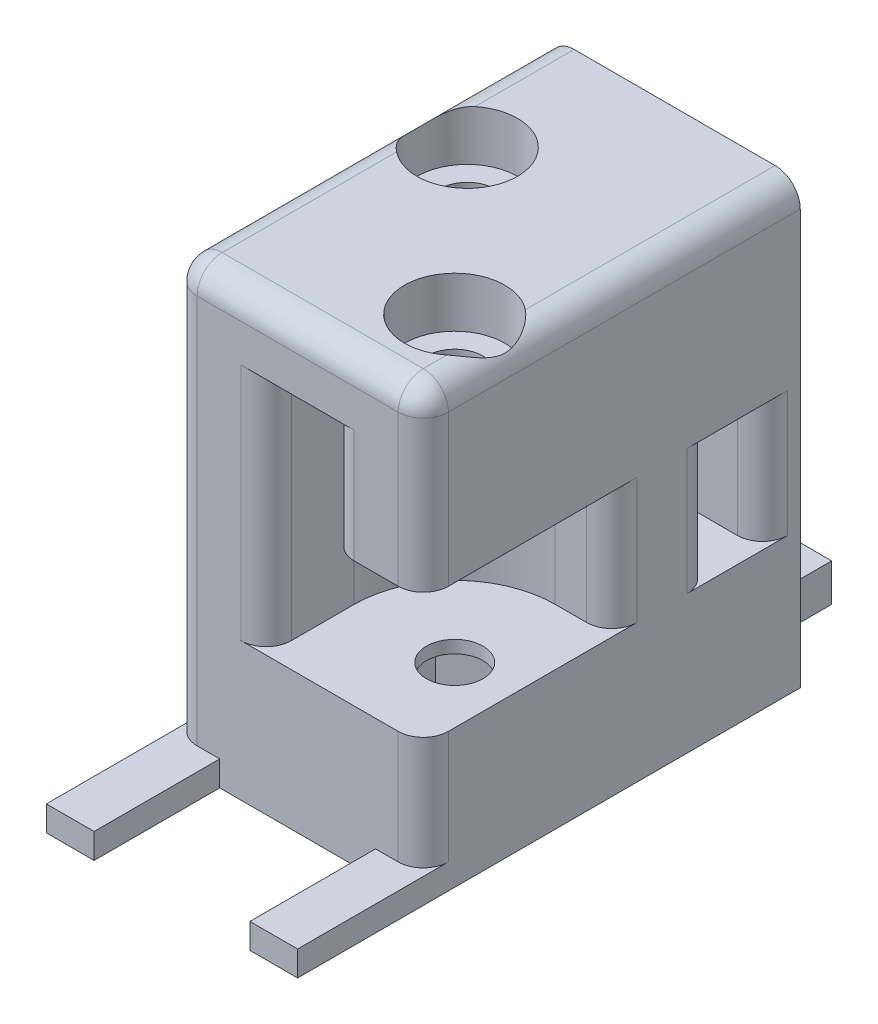
SolidWorks part; units mm, degrees
material "ABS"
ref_plane "Front Plane" through (0, 0, 0) normal (0, 0, 1) x (1, 0, 0)
ref_plane "Top Plane" through (0, 0, 0) normal (0, 1, 0) x (1, 0, 0)
ref_plane "Right Plane" through (0, 0, 0) normal (1, 0, 0) x (0, 0, -1)
sketch "Sketch2" plane through (0, 0, 0) normal (0, 1, 0) x (1, 0, 0)
  line L1 (-10, -15) -> (10, -15)
  line L2 (-10, -15) -> (-10, 15)
  line L3 (-10, 15) -> (10, 15)
  line L4 (10, -15) -> (10, 15)
  line L5 (-10, -15) -> (10, 15) construction
  line L6 (-10, 15) -> (10, -15) construction
  point P0 (0, 0)
  dimension "D1" = 20
  dimension "D2" = 30
extrude "Boss-Extrude1" add sketch "Sketch2" along normal blind 30
sketch "Sketch3" plane through (0, 30, 0) normal (0, 1, 0) x (1, 0, 0)
  line L0 (0, -15) -> (0, 15) construction
  line L1 (-10, -15) -> (10, -15) construction
  line L2 (10, 15) -> (-10, 15) construction
  line L3 (5.5, -1) -> (10, -1)
  line L4 (10, -15) -> (10, 15) construction
  line L6 (-5.5, 11) -> (-10, 11)
  line L7 (-10, 15) -> (-10, -15) construction
  line L8 (-10, 11) -> (-10, -1.3619)
  line L9 (-1.5, -8) -> (-1.5, -1.7446)
  line L10 (1.5, 4) -> (1.5, -2.2554)
  line L11 (-1.5, -8) -> (-1.5, -15)
  line L12 (1.5, -15) -> (1.5, -13.7446)
  line L13 (10, 11) -> (-5.5, 11)
  line L14 (10, 11) -> (10, 8)
  line L15 (10, 8) -> (0.2446, 8)
  line L17 (10, -15) -> (10, -1)
  line L18 (1.5, -15) -> (10, -15)
  line L19 (-5.5, -3) -> (-10, -3)
  line L20 (-10, -3) -> (-10, -1.3619)
  circle A0 centre (5.5, -8) radius 2.25
  circle A1 centre (-5.5, 4) radius 2.25
  arc A2 (5.5, -1) -> (1.5, -13.7446) centre (5.5, -8) ccw
  arc A3 (-5.5, 11) -> (-10, -1.3619) centre (-5.5, 4) cw
  line M1 (10, -15) -> (10, 15)
  line M3 (-10, 15) -> (-10, -15)
  line M4 (-10, -15) -> (10, -15)
  dimension "D3" = 4.5
  dimension "D4" = 4.5
  dimension "D7" = 7
  dimension "D8" = 7
  dimension "D1" = 5.5
  dimension "D2" = 7
  dimension "D5" = 12
  dimension "D6" = 5.5
  dimension "D9" = 3
extrude "Cut-Extrude2" cut sketch "Sketch3" against normal blind 19 contours L0 A2 L3 A0 M1 | A2 L0 | A3 L0 L6 A1 M3 | L0 A3 | L0 A2 L10 A3 | A2 L0 A3 L9 | L0 A2 L11 M4 | L0 L12 A2 M4 | L0 L15 L13 M1 | L15 L0 L13 A3 | L19 A3 M3 region at (-0.8553, 30, 12.8515) region at (0.6574, 30, 14.0101) region at (-0.6059, 30, 8) region at (0.172, 30, 8) region at (-0.8136, 30, 3.1846) region at (0.8136, 30, 0.8154) region at (-0.8157, 30, 0.9677) region at (0.6059, 30, -4) region at (-8.903, 30, 2.5203) region at (-1.3171, 30, -10.2343) region at (5.0068, 30, -9.5019)
sketch "Sketch5" plane through (0, 30, 0) normal (0, 1, 0) x (1, 0, 0)
  line L1 (10, -15) -> (-10, -15)
  line L2 (10, -15) -> (10, 15)
  line L3 (10, 15) -> (-10, 15)
  line L4 (-10, -15) -> (-10, 15)
  line L5 (10, -15) -> (-10, 15) construction
  line L6 (10, 15) -> (-10, -15) construction
  point P0 (0, 0)
extrude "Boss-Extrude2" add sketch "Sketch5" along normal blind 5
sketch "Sketch6" plane through (0, 30, 0) normal (0, -1, 0) x (1, 0, 0)
  line L3 (-1.5, 15) -> (10, 15) construction
  line L8 (1.5, 2.2554) -> (1.5, 15)
  line L9 (-1.5, 15) -> (10, 15) construction
  line L10 (1.5, 15) -> (10, 15)
  line L11 (10, 15) -> (10, 1)
  line L12 (10, 1) -> (5.5, 1)
  line L13 (5.5, 1) -> (10, 1) construction
  circle A0 centre (5.5, 8) radius 2.2812
  arc A1 (5.5, 1) -> (1.5, 2.2554) centre (5.5, 8) cw
extrude "Boss-Extrude3" add sketch "Sketch6" along normal blind 9
sketch "Sketch7" plane through (0, 11, 0) normal (0, 1, 0) x (1, 0, 0)
  line L0 (0.2446, 8) -> (-10, 8)
  line L1 (-5.5, -3) -> (-10, -3)
  line L2 (-10, 11) -> (-10, -3) construction
  line L3 (-1.5, -15) -> (-1.5, -1.7446) construction
  line L4 (-1.5, -1.7446) -> (-1.5, -8)
  line L5 (1.5, -2.2554) -> (1.5, 4)
  line L6 (1.5, 4) -> (1.5, -2.2554) construction
  line L7 (-10, 8) -> (-10, -3)
  arc A0 (0.2446, 8) -> (1.5, 4) centre (-5.5, 4) cw
  arc A1 (-1.5, -1.7446) -> (-5.5, -3) centre (-5.5, 4) cw
  arc A2 (-5.5, -3) -> (-1.5, -1.7446) centre (-5.5, 4) ccw construction
  arc A3 (1.5, -2.2554) -> (-1.5, -8) centre (5.5, -8) ccw
  circle A4 centre (-5.5, 4) radius 2.25
  arc A5 (-5.5, -3) -> (-1.5, -1.7446) centre (-5.5, 4) ccw construction
extrude "Boss-Extrude4" add sketch "Sketch7" along normal blind 9 contours A3 L0 region at (-4.0921, 11, -2.1111)
sketch "Sketch15" plane through (0, 30, 0) normal (0, -1, 0) x (1, 0, 0)
  line L0 (10, -11) -> (-10, -11) construction
  line L5 (10, -8) -> (10, -11)
  line L6 (10, -11) -> (-5.5, -11)
  line L7 (0.2446, -8) -> (10, -8)
  arc A0 (0.2446, -8) -> (-5.5, -11) centre (-5.5, -4) cw
extrude "Boss-Extrude6" add sketch "Sketch15" along normal blind 9
sketch "Sketch16" [suppressed] plane through (0, 11, 0) normal (0, 1, 0) x (1, 0, 0)
  line L0 (10, -15) -> (10, -1)
  line L1 (10, -1) -> (5.5, -1)
  line L2 (10, -15) -> (1.5, -15)
  line L3 (-1.5, -15) -> (10, -15) construction
  line L4 (1.5, -15) -> (1.5, -2.2554)
  circle A0 centre (5.5, -8) radius 2.25
  arc A1 (5.5, -1) -> (1.5, -2.2554) centre (5.5, -8) ccw construction
  arc A2 (1.5, -2.2554) -> (5.5, -1) centre (5.5, -8) cw
  dimension "D1" = 3
extrude "Boss-Extrude7" [suppressed] add sketch "Sketch16" along normal blind 9
sketch "Sketch17" [suppressed] plane through (0, 30, 0) normal (0, -1, 0) x (1, 0, 0)
  line L0 (0.2446, -8) -> (-10, -8)
  line L1 (-10, -11) -> (-10, 3) construction
  line L2 (-10, -8) -> (-10, 3)
  line L3 (1.5, -4) -> (1.5, 2.2554) construction
  line L4 (1.5, -4) -> (1.5, 2.2554)
  line L5 (-1.5, 8.0934) -> (-1.5, 1.7446)
  line L6 (-1.5, 15) -> (-1.5, 1.7446) construction
  line L7 (-5.5, 3) -> (-10, 3)
  line L8 (-5.5, 3) -> (-10, 3) construction
  circle A0 centre (-5.5, -4) radius 2.25
  arc A1 (-1.5, 1.7446) -> (-5.5, 3) centre (-5.5, -4) ccw
  arc A2 (-1.5, 1.7446) -> (-5.5, 3) centre (-5.5, -4) ccw construction
  arc A3 (0.2446, -8) -> (1.5, -4) centre (-5.5, -4) ccw
  arc A4 (1.5, 2.2554) -> (-1.5, 8) centre (5.5, 8) cw
  arc A5 (-1.5, 1.7446) -> (-5.5, 3) centre (-5.5, -4) ccw construction
extrude "Boss-Extrude8" [suppressed] add sketch "Sketch17" along normal blind 9
sketch "Sketch18" [suppressed] plane through (0, 11, 0) normal (0, 1, 0) x (1, 0, 0)
  line L0 (10, 11) -> (10, 8)
  line L1 (10, 8) -> (0.2446, 8)
  line L2 (10, 11) -> (-10, 11) construction
  line L3 (10, 11) -> (-5.5, 11)
  arc A0 (0.2446, 8) -> (-5.5, 11) centre (-5.5, 4) ccw
extrude "Boss-Extrude9" [suppressed] add sketch "Sketch18" along normal blind 9
sketch "Sketch9" plane through (0, 0, -15) normal (0, 0, -1) x (-1, 0, 0)
  line L0 (-10, 0) -> (10, 0) construction
  line L1 (-5.5, 3) -> (5.5, 3)
  line L2 (-5.5, 3) -> (-5.5, 0)
  line L3 (-5.5, 0) -> (5.5, 0)
  line L4 (5.5, 3) -> (5.5, 0)
  line L5 (-5.5, 3) -> (5.5, 0) construction
  line L6 (-5.5, 0) -> (5.5, 3) construction
  line L9 (-10, 35) -> (-10, 0) construction
  point P0 (0, 1.5)
  dimension "D1" = 3
  dimension "D2" = 11
  dimension "D3" = 4.5
extrude "Boss-Extrude5" add sketch "Sketch9" along normal blind 7
sketch "Sketch10" plane through (0, 3, 0) normal (0, 1, 0) x (1, 0, 0)
  line L0 (-5.5, 15) -> (5.5, 15) construction
  circle A0 centre (0, 18.5) radius 1.75
  dimension "D1" = 3.5
  dimension "D2" = 3.5
extrude "Cut-Extrude4" cut sketch "Sketch10" against normal through all
sketch "Sketch11" plane through (0, 3, 0) normal (0, 1, 0) x (1, 0, 0)
  circle A0 centre (0, 18.5) radius 3
  dimension "D1" = 6
extrude "Cut-Extrude5" cut sketch "Sketch11" against normal blind 1
sketch "Sketch8" plane through (0, 35, 0) normal (0, 1, 0) x (1, 0, 0)
  line L0 (0, -15) -> (0, 15) construction
  line L1 (-10, -15) -> (10, -15) construction
  line L2 (10, 15) -> (-10, 15) construction
  circle A0 centre (5.5, -8) radius 2.25
  circle A1 centre (-5.5, 4) radius 2.25
  dimension "D1" = 4.5
  dimension "D2" = 4.5
  dimension "D3" = 7
  dimension "D4" = 5.5
  dimension "D5" = 5.5
  dimension "D6" = 12
extrude "Cut-Extrude3" cut sketch "Sketch8" against normal through all
hole_wizard "CBORE for M4 Hex Socket Head Cap Screw1" positions "Sketch12" profile "Sketch13" counterbore size "M4" standard "ISO" end condition up to next
sketch "Sketch12" plane through (0, 35, 0) normal (0, 1, 0) x (1, 0, 0)
  point P0 (5.5, -8)
  point P3 (-5.5, 4)
sketch "Sketch13" plane through (5.5, 35, 8) normal (1, 0, 0) x (0, 0, 1)
  line L0 (0, 0) -> (0, 35)
  line L1 (0, 35) -> (2.25, 35)
  line L3 (2.25, 35) -> (2.25, 4)
  line L4 (2.25, 4) -> (4, 4)
  line L5 (4, 4) -> (4, 0)
  line L7 (4, 0) -> (0, 0)
  line L11 (0, -6.35) -> (0, 107.95) construction
  dimension "Thru Hole Dia." = 4.5
  dimension "Thru Hole Depth" = 35
  dimension "C'Bore Dia." = 8
  dimension "C'Bore Depth" = 4
sketch "Sketch14" plane through (0, 0, 0) normal (0, -1, 0) x (1, 0, 0)
  line L1 (5.5, 3.8142) -> (9.125, 5.9071)
  line L2 (9.125, 5.9071) -> (9.125, 10.0929)
  line L3 (9.125, 10.0929) -> (5.5, 12.1858)
  line L4 (5.5, 12.1858) -> (1.875, 10.0929)
  line L5 (1.875, 10.0929) -> (1.875, 5.9071)
  line L6 (1.875, 5.9071) -> (5.5, 3.8142)
  line L7 (-5.5, -8.1858) -> (-1.875, -6.0929)
  line L8 (-1.875, -6.0929) -> (-1.875, -1.9071)
  line L9 (-1.875, -1.9071) -> (-5.5, 0.1858)
  line L10 (-5.5, 0.1858) -> (-9.125, -1.9071)
  line L11 (-9.125, -1.9071) -> (-9.125, -6.0929)
  line L12 (-9.125, -6.0929) -> (-5.5, -8.1858)
  circle A0 centre (5.5, 8) radius 3.625 construction
  circle A1 centre (-5.5, -4) radius 3.625 construction
  dimension "D1" = 7.25
  dimension "D2" = 7.25
extrude "Cut-Extrude6" cut sketch "Sketch14" against normal blind 10
sketch "Sketch19" plane through (0, 0, 15) normal (0, 0, 1) x (1, 0, 0)
  line L1 (-10, 0) -> (-6.2, 0)
  line L2 (-10, 0) -> (-10, 2)
  line L3 (-10, 2) -> (-6.2, 2)
  line L4 (-6.2, 0) -> (-6.2, 2)
  line L5 (10, 0) -> (6.2, 0)
  line L6 (10, 0) -> (10, 2)
  line L7 (10, 2) -> (6.2, 2)
  line L8 (6.2, 0) -> (6.2, 2)
  dimension "D1" = 3.8
  dimension "D2" = 3.8
  dimension "D3" = 2
  dimension "D4" = 2
extrude "Boss-Extrude10" add sketch "Sketch19" along normal blind 10
sketch "Sketch21" [suppressed] plane through (0, 20, 0) normal (0, 1, 0) x (1, 0, 0)
  line L3 (10, 0) -> (5.5, 0)
  line L4 (10, -15) -> (-2.5, -15)
  line L5 (-2.5, -15) -> (-2.5, -8)
  line L6 (10, -15) -> (10, 0)
  arc A0 (5.5, 0) -> (-2.5, -8) centre (5.5, -8) ccw
  dimension "D1" = 8
extrude "Cut-Extrude8" [suppressed] cut sketch "Sketch21" along normal blind 10
sketch "Sketch23" [suppressed] plane through (0, 11, 0) normal (0, 1, 0) x (1, 0, 0)
  line L36 (-11, 12) -> (-11, -4)
  line L37 (-11, -4) -> (-5.5, -4)
  line L38 (-2.5, -3.4162) -> (-2.5, -16)
  line L39 (-2.5, -16) -> (2.5, -16)
  line L40 (2.5, -16) -> (2.5, 4)
  line L41 (-5.5, 12) -> (-11, 12)
  line L42 (-11, 12) -> (-11, -4)
  line L43 (-11, -4) -> (-5.5, -4)
  line L44 (-2.5, -3.4162) -> (-2.5, -16)
  line L45 (-2.5, -16) -> (2.5, -16)
  line L46 (2.5, -16) -> (2.5, 4)
  line L47 (-5.5, 12) -> (-11, 12)
  arc A12 (-5.5, -4) -> (-2.5, -3.4162) centre (-5.5, 4) ccw
  arc A13 (2.5, 4) -> (-5.5, 12) centre (-5.5, 4) ccw
  arc A14 (-5.5, -4) -> (-2.5, -3.4162) centre (-5.5, 4) ccw
  arc A15 (2.5, 4) -> (-5.5, 12) centre (-5.5, 4) ccw
  dimension "D1" = 1
extrude "Cut-Extrude9" [suppressed] cut sketch "Sketch23" along normal blind 10
sketch "Sketch27" [suppressed] plane through (-10, 0, 0) normal (-1, 0, 0) x (0, 0, 1)
  line L0 (-12, 21) -> (-12, 11) construction
  line L1 (-8, 30) -> (-12, 30)
  line L2 (-8, 30) -> (-8, 20)
  line L3 (-8, 20) -> (-12, 20)
  line L4 (-12, 30) -> (-12, 20)
  dimension "D1" = 10
extrude "Cut-Extrude13" [suppressed] cut sketch "Sketch27" against normal through all
sketch "Sketch24" plane through (0, 11, 0) normal (0, 1, 0) x (1, 0, 0)
  line L16 (-2.5, -16) -> (11, -16)
  line L17 (11, -16) -> (11, 0)
  line L18 (11, 0) -> (5.5, 0)
  line L19 (-2.5, -8) -> (-2.5, -16)
  line L20 (-2.5, -16) -> (11, -16)
  line L21 (11, -16) -> (11, 0)
  line L22 (11, 0) -> (5.5, 0)
  line L23 (-2.5, -8) -> (-2.5, -16)
  arc A6 (5.5, 0) -> (-2.5, -8) centre (5.5, -8) ccw
  arc A7 (5.5, 0) -> (-2.5, -8) centre (5.5, -8) ccw
  dimension "D1" = 1
extrude "Cut-Extrude10" cut sketch "Sketch24" along normal blind 10
sketch "Sketch25" plane through (0, 30, 0) normal (0, -1, 0) x (1, 0, 0)
  line L4 (-10, -12) -> (-10, 4)
  line L5 (2.5, -4) -> (2.5, 15)
  line L6 (-10, -12) -> (-5.5, -12)
  line L7 (2.5, -4) -> (2.5, 15)
  line L8 (-10, -12) -> (-5.5, -12)
  line L9 (-5.5, 4) -> (-10, 4)
  line L10 (-5.5, 4) -> (-10, 4)
  line L13 (2.5, 15) -> (-2.5, 15)
  line L15 (-2.5, 15) -> (-2.5, 3.4162)
  arc A4 (-5.5, -12) -> (2.5, -4) centre (-5.5, -4) ccw
  arc A5 (-5.5, -12) -> (2.5, -4) centre (-5.5, -4) ccw
  arc A7 (-5.5, 4) -> (-2.5, 3.4162) centre (-5.5, -4) cw
  arc A8 (-0.9286, 2.5652) -> (-5.5, 4) centre (-5.5, -4) ccw
  dimension "D3" = 5
  dimension "D1" = 1
  dimension "D2" = 1
extrude "Cut-Extrude11" cut sketch "Sketch25" along normal blind 10
sketch "Sketch26" plane through (-10, 0, 0) normal (-1, 0, 0) x (0, 0, 1)
  line L0 (-12, 20) -> (-12, 30) construction
  line L1 (-8, 11) -> (-12, 11)
  line L2 (-8, 11) -> (-8, 21)
  line L3 (-8, 21) -> (-12, 21)
  line L4 (-12, 11) -> (-12, 21)
  dimension "D1" = 10
extrude "Cut-Extrude12" cut sketch "Sketch26" against normal through all
mirror "Mirror1" [suppressed] of bodies 128 113
delete or keep bodies "Body-Delete/Keep 1" [suppressed] type keep bodies bodies 116
fillet "Fillet1-r" radius 2 6 edges at (10, 6.5, 15) (10, 28, 15) (-10, 18.5, 15) (-10, 35, 0) (10, 35, 0) (0, 35, 15)
fillet "Fillet2-r" radius 2 9 edges at (-2.5, 25, 3.4162) (-10, 25, 4) (-10, 15.5, -8) (-10, 20.5, -12) (2.5, 25.5, 15) (-2.5, 20.5, 15) (10, 16, 0) (10, 16, -12) (10, 16, -8)
fillet "Fillet3-r" [suppressed] radius 2
fillet "Fillet4-l" [suppressed] radius 2
fillet "Fillet5-l" [suppressed] radius 2
